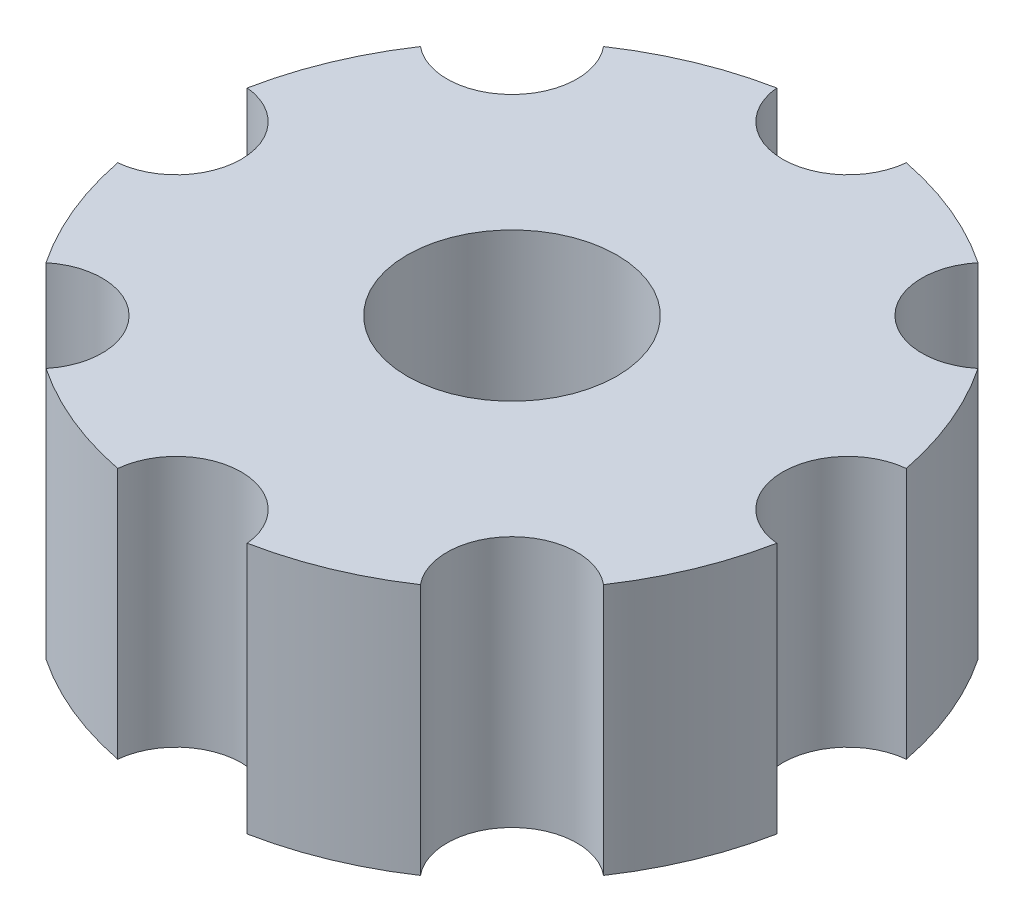
SolidWorks part; units mm, degrees
ref_plane "Front Plane" through (0, 0, 0) normal (0, 0, 1) x (1, 0, 0)
ref_plane "Top Plane" through (0, 0, 0) normal (0, 1, 0) x (1, 0, 0)
ref_plane "Right Plane" through (0, 0, 0) normal (1, 0, 0) x (0, 0, -1)
sketch "Sketch1" plane through (0, 0, 0) normal (0, 1, 0) x (1, 0, 0)
  circle A0 centre (0, 0) radius 8
  circle A1 centre (0, 0) radius 2.5
  circle A2 centre (0, 8) radius 1.55
  dimension "D1" = 16
  dimension "D2" = 5
  dimension "D3" = 3.1
extrude "Boss-Extrude1" add sketch "Sketch1" along normal blind 6 contours A2 A0 A1 | A0 A2 region at (-4.9392, 0, 6.0043) region at (0, 0, -7.3159)
extrude "Boss-Extrude2" add sketch "Sketch1<3>" along normal blind 2 contours A1
sketch "Sketch1<3>" plane through (0, 0, 0) normal (0, 1, 0) x (1, 0, 0) same geometry as "Sketch1"
ref_axis "Axis1" through (0, 0, 0) along (0, 1, 0)
extrude "Cut-Extrude1" cut sketch "Sketch1<4>" along normal through all contours A2
sketch "Sketch1<4>" plane through (0, 0, 0) normal (0, 1, 0) x (1, 0, 0) same geometry as "Sketch1"
pattern_circular "CirPattern1" count 8 over 360 about axis through (0, 0, 0) along (0, 1, 0) of "Cut-Extrude1"
